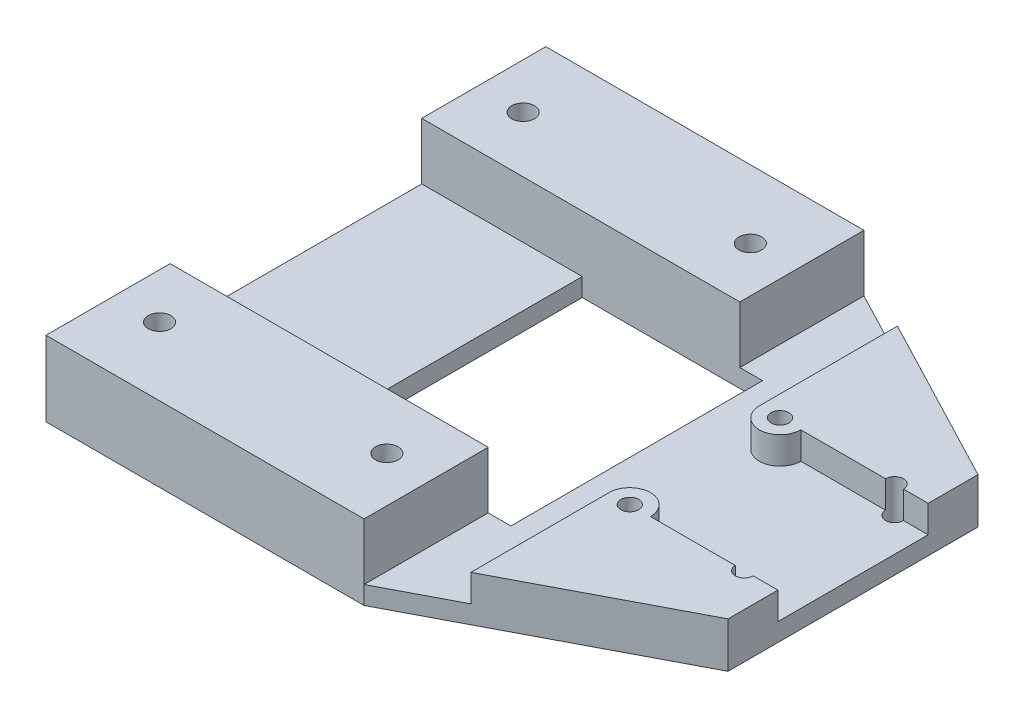
SolidWorks part; units mm, degrees
ref_plane "Front Plane" through (0, 0, 0) normal (0, 0, 1) x (1, 0, 0)
ref_plane "Top Plane" through (0, 0, 0) normal (0, 1, 0) x (1, 0, 0)
ref_plane "Right Plane" through (0, 0, 0) normal (1, 0, 0) x (0, 0, -1)
sketch "Sketch1" plane through (0, 0, 0) normal (0, 1, 0) x (1, 0, 0)
  line L0 (55.625, 17.4625) -> (22.225, 34.925)
  line L1 (-15.875, -25.4) -> (15.875, -25.4) construction
  line L2 (-15.875, -25.4) -> (-15.875, 25.4) construction
  line L3 (-15.875, 25.4) -> (15.875, 25.4) construction
  line L4 (15.875, -25.4) -> (15.875, 25.4) construction
  line L5 (-15.875, -25.4) -> (15.875, 25.4) construction
  line L6 (-15.875, 25.4) -> (15.875, -25.4) construction
  line L7 (22.225, -34.925) -> (-22.225, -34.925)
  line L8 (22.225, -34.925) -> (22.225, 34.925) construction
  line L9 (22.225, 34.925) -> (-22.225, 34.925)
  line L10 (-22.225, -34.925) -> (-22.225, 34.925)
  line L11 (22.225, -34.925) -> (-22.225, 34.925) construction
  line L12 (22.225, 34.925) -> (-22.225, -34.925) construction
  line L13 (34.925, -10.5) -> (50.925, -10.5) construction
  line L14 (34.925, -10.5) -> (34.925, 10.5) construction
  line L15 (34.925, 10.5) -> (50.925, 10.5) construction
  line L16 (50.925, -10.5) -> (50.925, 10.5) construction
  line L17 (34.925, -10.5) -> (50.925, 10.5) construction
  line L18 (34.925, 10.5) -> (50.925, -10.5) construction
  line L19 (30.225, 17.4625) -> (55.625, 17.4625) construction
  line L20 (30.225, 17.4625) -> (30.225, -17.4625) construction
  line L21 (30.225, -17.4625) -> (55.625, -17.4625) construction
  line L22 (55.625, 17.4625) -> (55.625, -17.4625)
  line L23 (30.225, 17.4625) -> (55.625, -17.4625) construction
  line L24 (30.225, -17.4625) -> (55.625, 17.4625) construction
  line L25 (55.625, -17.4625) -> (22.225, -34.925)
  circle A0 centre (-15.875, 25.4) radius 1.5875
  circle A1 centre (15.875, 25.4) radius 1.5875
  circle A2 centre (15.875, -25.4) radius 1.5875
  circle A3 centre (-15.875, -25.4) radius 1.5875
  circle A4 centre (50.925, 10.5) radius 1.25
  circle A5 centre (50.925, -10.5) radius 1.25
  circle A6 centre (34.925, -10.5) radius 1.25
  circle A8 centre (34.925, 10.5) radius 1.25
  point P0 (0, 0)
  point P7 (0, 0)
  point P15 (42.925, 0)
  point P21 (63.245, -16.6713)
  point P23 (42.925, 0)
  point P26 (0, 0)
  dimension "D3" = 3.175
  dimension "D8" = 2.5
  dimension "D1" = 50.8
  dimension "D2" = 31.75
  dimension "D4" = 69.85
  dimension "D5" = 6.35
  dimension "D6" = 21
  dimension "D7" = 16
  dimension "D9" = 25.4
  dimension "D10" = 34.925
  dimension "D11" = 12.7
extrude "Boss-Extrude1" add sketch "Sketch1" along normal blind 2.54
sketch "Sketch2" plane through (0, 2.54, 0) normal (0, 1, 0) x (1, 0, 0)
  line L5 (22.225, 17.582) -> (25.4, 17.582)
  line L6 (22.225, 17.582) -> (0.2018, 17.582)
  line L7 (22.225, 17.582) -> (22.225, -17.582) construction
  line L8 (22.225, 17.582) -> (22.225, -17.582) construction
  line L9 (22.225, -17.582) -> (0.2018, -17.582)
  line L10 (0.2018, 17.582) -> (0.2018, -17.582)
  line L11 (22.225, 17.582) -> (0.2018, -17.582) construction
  line L12 (22.225, -17.582) -> (0.2018, 17.582) construction
  line L13 (22.225, -17.582) -> (25.4, -17.582)
  line L14 (25.4, 17.582) -> (25.4, -17.582)
  point P0 (0, 0)
  point P1 (11.2134, 0)
  dimension "D1" = 3.175
extrude "Cut-Extrude1" cut sketch "Sketch2" against normal blind 2.54
sketch "Sketch3" plane through (0, 2.54, 0) normal (0, 1, 0) x (1, 0, 0)
  line L5 (55.625, -17.4625) -> (55.625, 17.4625) construction
  line L8 (55.625, 10.5) -> (52.175, 10.5)
  line L9 (0, 0) -> (25.4, 0) construction
  line L10 (25.4, -17.582) -> (25.4, 17.582) construction
  line L17 (55.625, -17.4625) -> (55.625, -10.5)
  line L18 (49.675, 10.5) -> (37.8235, 10.5)
  line L20 (32.0265, 10.5) -> (32.0265, 29.8005)
  line L21 (55.625, 17.4625) -> (22.225, 34.925) construction
  line L22 (32.0265, 29.8005) -> (55.625, 17.4625)
  line L23 (55.625, 17.4625) -> (55.625, 10.5)
  line L24 (32.0265, -29.8005) -> (55.625, -17.4625)
  line L25 (32.0265, -10.5) -> (32.0265, -29.8005)
  line L26 (49.675, -10.5) -> (37.8235, -10.5)
  line L27 (55.625, -10.5) -> (52.175, -10.5)
  circle A0 centre (50.925, 10.5) radius 1.25 construction
  circle A1 centre (34.925, 10.5) radius 1.25 construction
  arc A3 (32.0265, -10.5) -> (37.8235, -10.5) centre (34.925, -10.5) cw
  arc A6 (52.175, -10.5) -> (49.675, -10.5) centre (50.925, -10.5) cw
  circle A12 centre (34.925, 10.5) radius 1.25
  arc A13 (52.175, 10.5) -> (49.675, 10.5) centre (50.925, 10.5) ccw
  arc A14 (32.0265, 10.5) -> (37.8235, 10.5) centre (34.925, 10.5) ccw
  circle A15 centre (34.925, -10.5) radius 1.25
extrude "Boss-Extrude2" add sketch "Sketch3" along normal blind 3.81
sketch "Sketch5" plane through (0, 2.54, 0) normal (0, 1, 0) x (1, 0, 0)
  line L0 (25.4, 17.582) -> (0.2018, 17.582) construction
  line L1 (-22.225, 34.925) -> (22.225, 34.925)
  line L2 (-22.225, 34.925) -> (-22.225, 17.582)
  line L3 (-22.225, 17.582) -> (22.225, 17.582)
  line L4 (22.225, 34.925) -> (22.225, 17.582)
  line L5 (-22.225, 34.925) -> (-22.225, -34.925) construction
  line L6 (22.225, -34.925) -> (-22.225, -34.925)
  line L8 (22.225, -17.582) -> (-22.225, -17.582)
  line L9 (-22.225, -34.925) -> (-22.225, -17.582)
  line L12 (22.225, -34.925) -> (22.225, -17.582)
  circle A0 centre (15.875, -25.4) radius 1.5875
  circle A1 centre (-15.875, -25.4) radius 1.5875
  circle A2 centre (-15.875, 25.4) radius 1.5875
  circle A3 centre (15.875, 25.4) radius 1.5875
extrude "Boss-Extrude3" add sketch "Sketch5" along normal blind 7.9375
